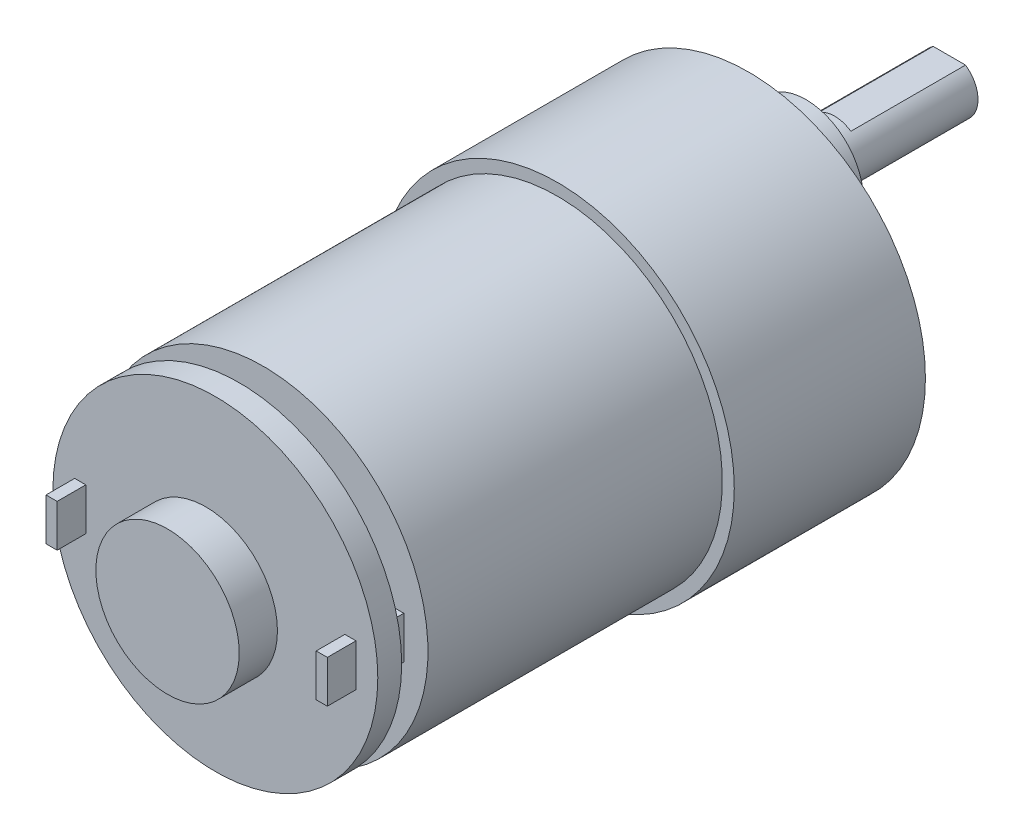
SolidWorks part; units mm, degrees
ref_plane "Front Plane" through (0, 0, 0) normal (0, 0, 1) x (1, 0, 0)
ref_plane "Top Plane" through (0, 0, 0) normal (0, 1, 0) x (1, 0, 0)
ref_plane "Right Plane" through (0, 0, 0) normal (1, 0, 0) x (0, 0, -1)
sketch "Sketch1" plane through (0, 0, 0) normal (0, 0, 1) x (1, 0, 0)
  circle A1 centre (0, 0) radius 18.5
  dimension "D1" = 37
extrude "Boss-Extrude2" add sketch "Sketch1" against normal blind 20 contours A1
sketch "Sketch2" plane through (0, 0, 0) normal (0, 0, 1) x (1, 0, 0)
  circle A0 centre (0, 0) radius 17.25
  dimension "D1" = 34.5
extrude "Boss-Extrude3" add sketch "Sketch2" along normal blind 30.8
sketch "Sketch3" plane through (0, 0, 30.8) normal (0, 0, 1) x (1, 0, 0)
  circle A0 centre (0, 0) radius 1.5
  dimension "D1" = 3
extrude "Boss-Extrude4" add sketch "Sketch3" along normal blind 5
sketch "Sketch5" plane through (0, 0, 30.8) normal (0, 0, 1) x (1, 0, 0)
  line L0 (14.7177, 2.2141) -> (13.5529, 2.2141)
  line L1 (-14.7177, 2.2141) -> (-13.5529, 2.2141)
  line L2 (-14.7177, 2.2141) -> (-14.7177, -2.2141)
  line L3 (-14.7177, -2.2141) -> (-13.5529, -2.2141)
  line L4 (-13.5529, 2.2141) -> (-13.5529, -2.2141)
  line L5 (-14.7177, 2.2141) -> (-13.5529, -2.2141) construction
  line L6 (-14.7177, -2.2141) -> (-13.5529, 2.2141) construction
  line L7 (13.5529, -2.2141) -> (13.5529, 2.2141)
  line L8 (14.7177, -2.2141) -> (14.7177, 2.2141)
  line L9 (14.7177, -2.2141) -> (13.5529, -2.2141)
  circle A0 centre (0, 0) radius 14.1353 construction
  point P3 (-14.1353, 0)
  point P14 (0, 0)
  dimension "D1" = 2
extrude "Boss-Extrude9" add sketch "Sketch5" along normal blind 8
sketch "Sketch6" plane through (0, 0, -20) normal (0, 0, -1) x (-1, 0, 0)
  circle A0 centre (0, 7) radius 6
  dimension "D2" = 12
extrude "Boss-Extrude12" add sketch "Sketch6" along normal blind 6
sketch "Sketch9" plane through (0, 0, -26) normal (0, 0, -1) x (-1, 0, 0)
  circle A0 centre (0, 7) radius 3
  dimension "D1" = 6
extrude "Boss-Extrude13" add sketch "Sketch9" along normal blind 15
sketch "Sketch10" plane through (0, 0, -41) normal (0, 0, -1) x (-1, 0, 0)
  line L5 (-3.0169, 10.4749) -> (3.0169, 10.4749)
  line L6 (-3.0169, 10.4749) -> (-3.0169, 9.4749)
  line L7 (-3.0169, 9.4749) -> (3.0169, 9.4749)
  line L8 (3.0169, 10.4749) -> (3.0169, 9.4749)
  line L9 (-3.0169, 10.4749) -> (3.0169, 9.4749) construction
  line L10 (-3.0169, 9.4749) -> (3.0169, 10.4749) construction
  circle A0 centre (0, 7) radius 3 construction
  circle A1 centre (0, 7) radius 3 construction
  point P0 (-0.3876, 9.9749)
  point P1 (0, 9.9749)
  dimension "D1" = 1
extrude "Cut-Extrude1" cut sketch "Sketch10" against normal blind 12
sketch "Sketch11" plane through (0, 0, -20) normal (0, 0, -1) x (-1, 0, 0)
  line L0 (0, 0) -> (0, 22.7851) construction
  line L1 (0, 0) -> (-13.4234, 7.75) construction
  circle A0 centre (0, 0) radius 15.5 construction
  circle A1 centre (-13.4234, 7.75) radius 1.5
  circle A2 centre (13.4234, 7.75) radius 1.5
  circle A3 centre (0, 0) radius 15.5 construction
  circle A4 centre (0, -15.5) radius 1.5
  circle A5 centre (0, 0) radius 15.5 construction
  circle A6 centre (-7.75, 13.4234) radius 1.5
  circle A8 centre (7.75, 13.4234) radius 1.5
  circle A9 centre (13.4234, 7.75) radius 1.5
  circle A10 centre (15.5, 0) radius 1.5
  circle A12 centre (7.75, -13.4234) radius 1.5
  circle A13 centre (0, -15.5) radius 1.5
  circle A14 centre (-7.75, -13.4234) radius 1.5
  circle A16 centre (-15.5, 0) radius 1.5
  circle A17 centre (0, 15.5) radius 1.5 [skipped]
  circle A18 centre (13.4234, -7.75) radius 1.5 [skipped]
  circle A19 centre (-13.4234, -7.75) radius 1.5 [skipped]
  point P15 (0, 0)
  point P38 (0, 0)
  dimension "D1" = 31
  dimension "D2" = 3
  dimension "D3" = 60
  dimension "D4" = 3
  dimension "D5" = 12
extrude "Cut-Extrude4" cut sketch "Sketch11" against normal blind 5 contours A8 | A10 | A12 | A4 | A14 | A16 | A1 | A6 | A2 region at (13.4234, 7.75, -20) region at (0, -15.5, -20) region at (-7.75, 13.4234, -20) region at (-15.5, 0, -20) region at (-7.75, -13.4234, -20) region at (7.75, -13.4234, -20) region at (15.5, 0, -20)
sketch "Sketch12" plane through (0, 0, -20) normal (0, 0, -1) x (-1, 0, 0)
  arc A0 (-9.997, 5.2333) -> (9.9299, 5.2333) centre (-0.0335, -0.3871) ccw
  arc A1 (-9.997, 5.2333) -> (9.9299, 5.2333) centre (-0.0335, 8.6729) ccw
extrude "Cut-Extrude5" cut sketch "Sketch12" against normal blind 0.5
sketch "Sketch13" plane through (0, 0, 35.8) normal (0, 0, 1) x (1, 0, 0)
  circle A0 centre (0, 0) radius 17
  dimension "D1" = 34
extrude "Boss-Extrude14" add sketch "Sketch13" against normal blind 2.5
sketch "Sketch15" plane through (0, 0, 35.8) normal (0, 0, 1) x (1, 0, 0)
  circle A0 centre (0, 0) radius 1.4897
  dimension "D1" = 2.9794
extrude "Boss-Extrude16" add sketch "Sketch15" along normal blind 1
sketch "Sketch16" plane through (0, 0, 36.8) normal (0, 0, 1) x (1, 0, 0)
  circle A0 centre (0, 0) radius 7.5
  dimension "D1" = 15
extrude "Boss-Extrude17" add sketch "Sketch16" along normal blind 4
